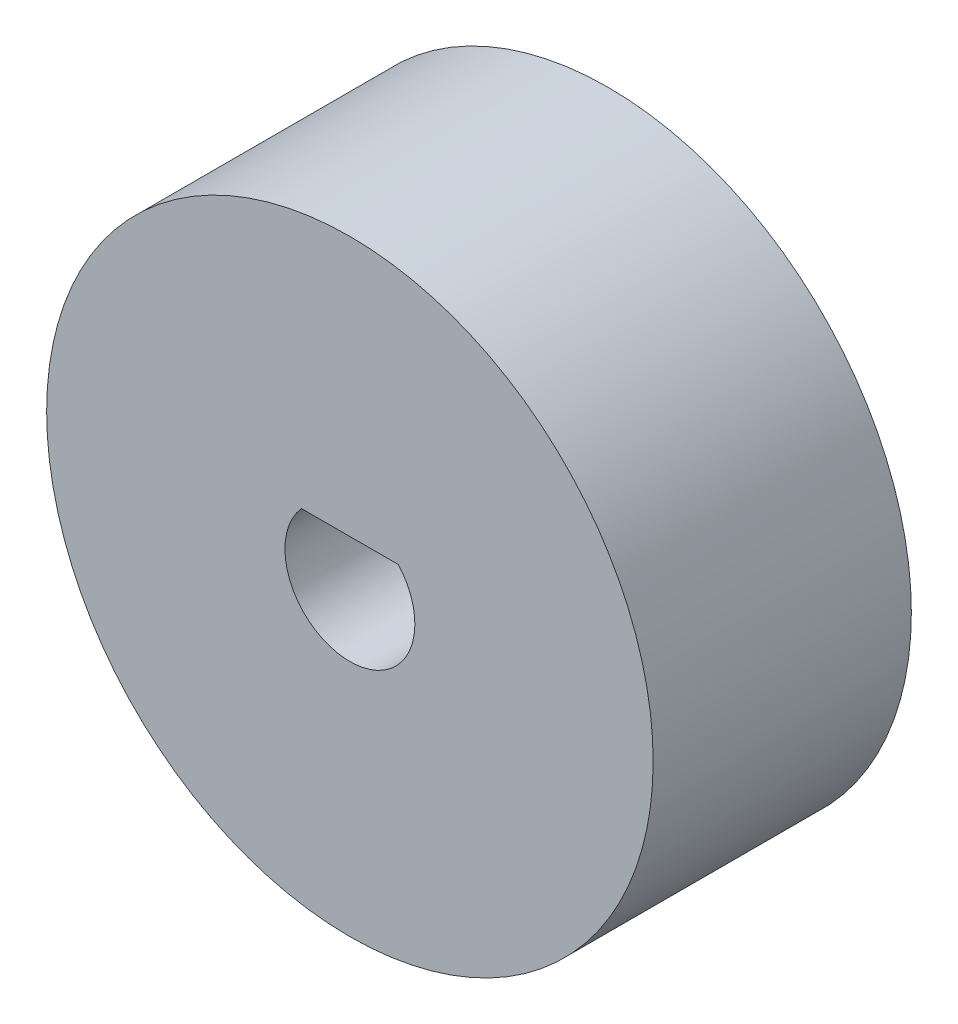
SolidWorks part; units mm, degrees
ref_plane "Front Plane" through (0, 0, 0) normal (0, 0, 1) x (1, 0, 0)
ref_plane "Top Plane" through (0, 0, 0) normal (0, 1, 0) x (1, 0, 0)
ref_plane "Right Plane" through (0, 0, 0) normal (1, 0, 0) x (0, 0, -1)
sketch "Sketch1" plane through (0, 0, 0) normal (0, 0, 1) x (1, 0, 0)
  line L0 (0, 0) -> (12707.853, 0) construction
  line L1 (0, 0) -> (0, -12707.853) construction
  line L2 (-1.118, 1) -> (1.118, 1)
  circle A0 centre (0, 0) radius 7
  arc A1 (-1.118, 1) -> (1.118, 1) centre (0, 0) ccw
  circle A2 centre (0, 0) radius 2.5
  dimension "D1" = 14
  dimension "D2" = 3
  dimension "D4" = 5
  dimension "D3" = 1
extrude "Boss-Extrude2" add sketch "Sketch1" along normal mid plane 5.96 contours A0 A2 region at (-6.802, 0, 0)
extrude "Boss-Extrude3" add sketch "Sketch1<5>" along normal up to surface and the other way up to surface contours A2 A1 L2 region at (-2.4293, 0, 0) up to face at (2.5, 0, 2.98) other way up to face at (2.5, 0, -2.98)
sketch "Sketch1<5>" plane through (0, 0, 0) normal (0, 0, 1) x (1, 0, 0) same geometry as "Sketch1"
